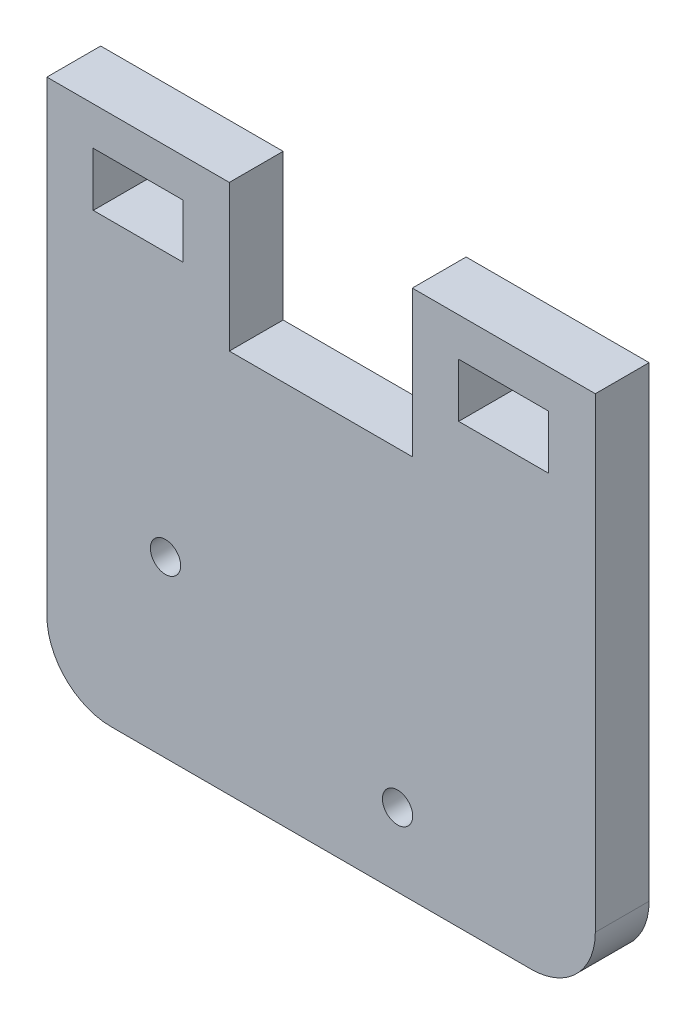
SolidWorks part; units mm, degrees
material "Teak"
ref_plane "Front Plane" through (0, 0, 0) normal (0, 0, 1) x (1, 0, 0)
ref_plane "Top Plane" through (0, 0, 0) normal (0, 1, 0) x (1, 0, 0)
ref_plane "Right Plane" through (0, 0, 0) normal (1, 0, 0) x (0, 0, -1)
sketch "Sketch1" plane through (0, 0, 0) normal (0, 0, 1) x (1, 0, 0)
  line L1 (-30.5325, 25.3111) -> (23.8235, 25.3111)
  line L2 (-30.5325, 25.3111) -> (-30.5325, -18.1229)
  line L3 (-30.5325, -18.1229) -> (23.8235, -18.1229)
  line L4 (23.8235, 25.3111) -> (23.8235, -18.1229)
  dimension "D1" = 43.434
  dimension "D2" = 54.356
extrude "Boss-Extrude1" add sketch "Sketch1" along normal blind 5.334 contours L1 L4 L3 L2
sketch "Sketch2" plane through (0, 0, 5.334) normal (0, 0, 1) x (1, 0, 0)
  line L0 (-30.5325, 25.3111) -> (23.8235, 25.3111) construction
  line L1 (-12.4506, 25.3111) -> (5.6865, 25.3111)
  line L2 (-12.4506, 25.3111) -> (-12.4506, 19.9771)
  line L3 (-12.4506, 19.9771) -> (5.6865, 19.9771)
  line L4 (5.6865, 25.3111) -> (5.6865, 19.9771)
  line L5 (-12.4506, 19.9771) -> (-30.5325, 19.9771) construction
  line L6 (-30.5325, 25.3111) -> (-30.5325, -18.1229) construction
  line L7 (5.6865, 19.9771) -> (23.8235, 19.9771) construction
  line L8 (23.8235, 25.3111) -> (23.8235, -18.1229) construction
  dimension "D1" = 5.334
extrude "Cut-Extrude1" cut sketch "Sketch2" against normal through all
fillet "Fillet1" radius 6.35 2 edges at (-30.5325, -18.1229, 2.667) (23.8235, -18.1229, 2.667)
sketch "Sketch3" plane through (0, 0, 5.334) normal (0, 0, 1) x (1, 0, 0)
  line L8 (-30.5325, 25.3111) -> (-30.5325, -11.7729)
  line L9 (-24.1825, -18.1229) -> (17.4735, -18.1229)
  line L10 (23.8235, -11.7729) -> (23.8235, 25.3111)
  line L11 (23.8235, 25.3111) -> (5.6865, 25.3111)
  line L12 (5.6865, 25.3111) -> (5.6865, 19.9771)
  line L13 (5.6865, 19.9771) -> (-12.4506, 19.9771)
  line L14 (-12.4506, 19.9771) -> (-12.4506, 25.3111)
  line L15 (-12.4506, 25.3111) -> (-30.5325, 25.3111)
  line L16 (-30.5325, 25.3111) -> (-30.5325, -11.7729)
  line L17 (-24.1825, -18.1229) -> (17.4735, -18.1229)
  line L18 (23.8235, -11.7729) -> (23.8235, 25.3111)
  line L19 (23.8235, 25.3111) -> (5.6865, 25.3111)
  line L20 (5.6865, 25.3111) -> (5.6865, 19.9771)
  line L21 (5.6865, 19.9771) -> (-12.4506, 19.9771)
  line L22 (-12.4506, 19.9771) -> (-12.4506, 25.3111)
  line L23 (-12.4506, 25.3111) -> (-30.5325, 25.3111)
  circle A0 centre (-18.7754, -0.8561) radius 1.5 construction
  circle A1 centre (4.2246, -10.8561) radius 1.5 construction
  arc A2 (-30.5325, -11.7729) -> (-24.1825, -18.1229) centre (-24.1825, -11.7729) ccw
  arc A3 (17.4735, -18.1229) -> (23.8235, -11.7729) centre (17.4735, -11.7729) ccw
  arc A4 (-30.5325, -11.7729) -> (-24.1825, -18.1229) centre (-24.1825, -11.7729) ccw
  arc A5 (17.4735, -18.1229) -> (23.8235, -11.7729) centre (17.4735, -11.7729) ccw
  circle A6 centre (-18.7754, -0.8561) radius 1.5
  circle A7 centre (4.2246, -10.8561) radius 1.5
  dimension "D1" = 0
extrude "Cut-Extrude3" cut sketch "Sketch3" against normal through all contours A6 | A7
sketch "Sketch4" plane through (0, 25.3111, 0) normal (0, 1, 0) x (1, 0, 0)
  line L1 (-30.5325, 0) -> (-12.4506, 0)
  line L2 (-30.5325, 0) -> (-30.5325, -5.334)
  line L3 (-30.5325, -5.334) -> (-12.4506, -5.334)
  line L4 (-12.4506, 0) -> (-12.4506, -5.334)
  line L5 (5.6865, 0) -> (23.8235, 0)
  line L6 (5.6865, 0) -> (5.6865, -5.334)
  line L7 (5.6865, -5.334) -> (23.8235, -5.334)
  line L8 (23.8235, 0) -> (23.8235, -5.334)
extrude "Boss-Extrude2" add sketch "Sketch4" along normal blind 9.144
sketch "Sketch5" plane through (0, 0, 5.334) normal (0, 0, 1) x (1, 0, 0)
  line L0 (-21.4915, 34.4551) -> (-21.4915, 17.922) construction
  line L1 (-25.9365, 30.6451) -> (-17.0465, 30.6451)
  line L2 (-25.9365, 30.6451) -> (-25.9365, 25.3111)
  line L3 (-25.9365, 25.3111) -> (-17.0465, 25.3111)
  line L4 (-17.0465, 30.6451) -> (-17.0465, 25.3111)
  line L5 (-30.5325, 34.4551) -> (-12.4506, 34.4551) construction
  line L6 (-12.4506, 19.9771) -> (5.6865, 19.9771) construction
  line L7 (-3.3821, 19.9771) -> (-3.3821, 43.7763) construction
  line L8 (10.2824, 30.6451) -> (10.2824, 25.3111)
  line L9 (19.1724, 25.3111) -> (10.2824, 25.3111)
  line L10 (19.1724, 30.6451) -> (19.1724, 25.3111)
  line L11 (19.1724, 30.6451) -> (10.2824, 30.6451)
  dimension "D1" = 5.334
  dimension "D2" = 8.89
  dimension "D3" = 4.445
  dimension "D4" = 5.334
extrude "Cut-Extrude4" cut sketch "Sketch5" against normal through all
equation "\"MDF\"= .21in"
equation "\"Foamcore\"= .13in"
equation "\"Gmaterial\"= \"MDF\""
equation "\"D1@Sketch1\"=\"MDF\"+1.5"
equation "\"D1@Boss-Extrude1\"=\"MDF\""
equation "\"D1@Sketch2\"=\"MDF\""
equation "\"D1@Sketch5\"=\"MDF\""
equation "\"D4@Sketch5\"=\"MDF\""
